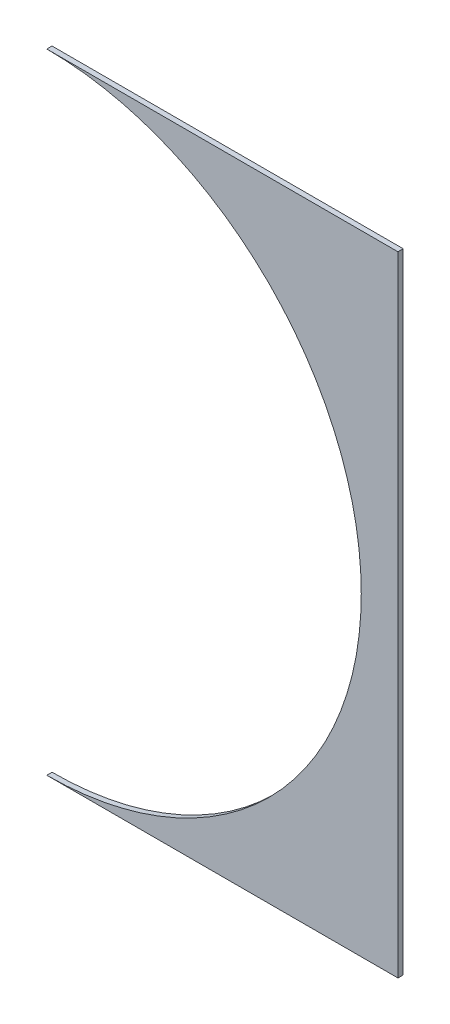
SolidWorks part; units mm, degrees
ref_plane "Front Plane" through (0, 0, 0) normal (0, 0, 1) x (1, 0, 0)
ref_plane "Top Plane" through (0, 0, 0) normal (0, 1, 0) x (1, 0, 0)
ref_plane "Right Plane" through (0, 0, 0) normal (1, 0, 0) x (0, 0, -1)
sketch "Sketch1" plane through (0, 0, 0) normal (0, 0, 1) x (1, 0, 0)
  line L1 (0, 0) -> (212.725, 0)
  line L2 (0, 0) -> (0, 381)
  line L3 (0, 381) -> (212.725, 381)
  line L4 (212.725, 0) -> (212.725, 381)
  arc A0 (0, 0) -> (0, 381) centre (0, 190.5) ccw
  dimension "D1" = 381
  dimension "D2" = 212.725
extrude "Boss-Extrude1" add sketch "Sketch1" along normal blind 3.175 contours A0 L1 L4 L3 region at (194.8636, 190.5, 0)
